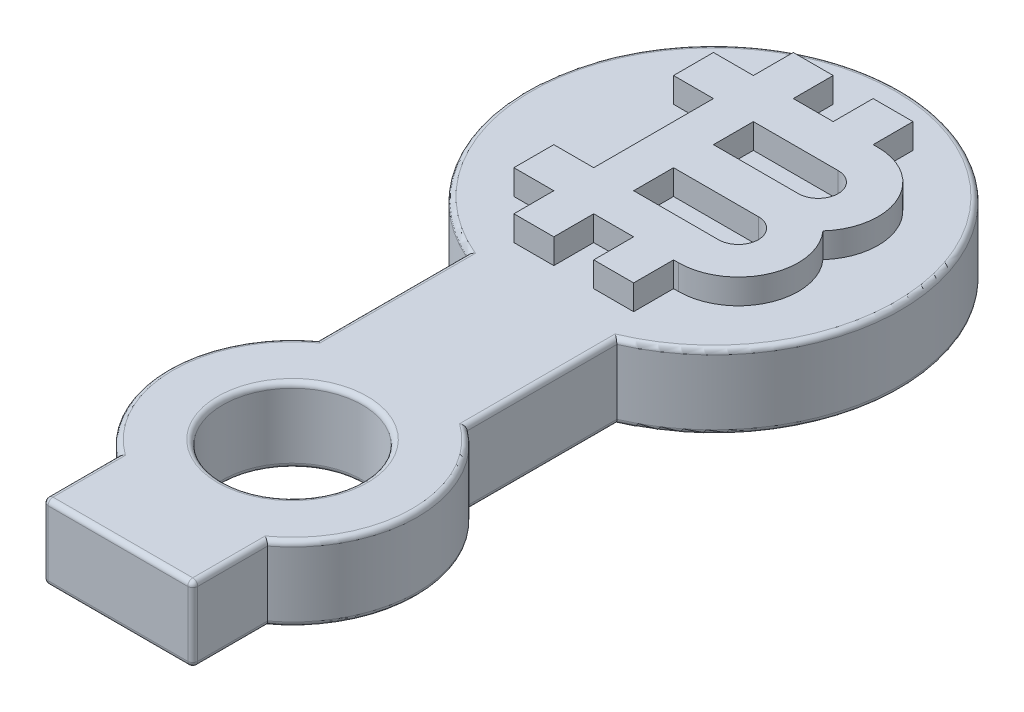
SolidWorks part; units mm, degrees
ref_plane "前视基准面" through (0, 0, 0) normal (0, 0, 1) x (1, 0, 0)
ref_plane "上视基准面" through (0, 0, 0) normal (0, 1, 0) x (1, 0, 0)
ref_plane "右视基准面" through (0, 0, 0) normal (1, 0, 0) x (0, 0, -1)
other "Configuration Table"
sketch "草图4" plane through (0, 0, 0) normal (0, 1, 0) x (1, 0, 0)
  line L0 (-3, 4) -> (-3, 10)
  line L2 (3, 10) -> (3, 4)
  line L3 (-3, -4) -> (-3, -7)
  line L4 (-3, -7) -> (3, -7)
  line L5 (3, -7) -> (3, -4)
  line L6 (0, 0) -> (0, 16.8739) construction
  circle A0 centre (0, 0) radius 2.8
  circle A1 centre (0, 0) radius 5
  circle A2 centre (0, 16.8739) radius 7.5
  dimension "D1" = 5.6
  dimension "D2" = 10
  dimension "D3" = 15
  dimension "D4" = 6
  dimension "D5" = 3
  dimension "D6" = 6
extrude "凸台-拉伸2" add sketch "草图4" along normal blind 3 contours A2 | A1 L6 A2 L0 | L6 A1 L2 A2 | A0 A1 | A1 L3 L4 L5 region at (-1.5364, 0, -4.6093) region at (-1.5815, 0, -7.1249) region at (-3.9917, 0, -22.9713) region at (0, 0, 5.8221) region at (1.5815, 0, -7.1249)
fillet "圆角1" radius 0.2 20 edges at (0, 0, 2.8) (-5, 0, 0) (-3, 0, 5.5) (0, 0, 7) (3, 0, 5.5) (5, 0, 0) (3, 0, -7) (0, 0, -24.3739) (-3, 0, -7) (0, 3, -24.3739) (3, 3, -7) (5, 3, 0) (3, 3, 5.5) (0, 3, 7) (-3, 3, 5.5) (-5, 3, 0) (-3, 3, -7) (0, 3, 2.8) (3, 1.5, 7) (-3, 1.5, 7)
sketch "草图1" plane through (0, 3, 0) normal (0, 1, 0) x (1, 0, 0)
  line L1 (-15.5883, 16.8739) -> (31.6232, 16.8739) construction
  line L2 (-0.8, 17.6739) -> (2.6, 17.6739)
  line L3 (-0.8, 17.6739) -> (-0.8, 19.2739)
  line L4 (-0.8, 19.2739) -> (2.6, 19.2739)
  line L5 (2.6, 16.0739) -> (-0.8, 16.0739)
  line L6 (-0.8, 16.0739) -> (-0.8, 14.4739)
  line L7 (-0.8, 14.4739) -> (2.6, 14.4739)
  line L9 (-0.8, 22.4739) -> (-2.4, 22.4739)
  line L10 (-2.4, 22.4739) -> (-2.4, 20.8739)
  line L11 (-2.4, 20.8739) -> (-4, 20.8739)
  line L12 (-4, 20.8739) -> (-4, 19.2739)
  line L13 (-4, 19.2739) -> (-2.4, 19.2739)
  line L14 (-2.4, 19.2739) -> (-2.4, 14.4739)
  line L15 (-4, 14.4739) -> (-4, 12.8739)
  line L16 (-4, 12.8739) -> (-2.4, 12.8739)
  line L17 (-2.4, 14.4739) -> (-4, 14.4739)
  line L18 (2.4, 20.8739) -> (2.6, 20.8739)
  line L19 (-2.4, 12.8739) -> (-2.4, 11.2739)
  line L20 (-2.4, 11.2739) -> (-0.8, 11.2739)
  line L22 (2.4, 12.8739) -> (2.6, 12.8739)
  line L23 (-0.8, 22.4739) -> (-0.8, 20.8739)
  line L24 (-0.8, 20.8739) -> (0.8, 20.8739)
  line L25 (0.8, 20.8739) -> (0.8, 22.4739)
  line L26 (0.8, 22.4739) -> (2.4, 22.4739)
  line L28 (2.4, 12.8739) -> (2.4, 11.2739)
  line L29 (2.4, 11.2739) -> (0.8, 11.2739)
  line L30 (0.8, 11.2739) -> (0.8, 12.8739)
  line L31 (0.8, 12.8739) -> (-0.8, 12.8739)
  line L32 (-0.8, 12.8739) -> (-0.8, 11.2739)
  line L33 (2.4, 20.8739) -> (2.4, 22.4739)
  arc A0 (2.6, 19.2739) -> (2.6, 17.6739) centre (2.6, 18.4739) cw
  arc A1 (2.6, 16.0739) -> (2.6, 14.4739) centre (2.6, 15.2739) cw
  arc A2 (2.6, 20.8739) -> (4.3889, 16.8739) centre (2.6, 18.4739) cw
  arc A3 (2.6, 12.8739) -> (4.3889, 16.8739) centre (2.6, 15.2739) ccw
  arc A4 (-3, 10) -> (3, 23.7477) centre (0, 16.8739) ccw construction
  arc A5 (-3, 10) -> (3, 23.7477) centre (0, 16.8739) ccw construction
  point P69 (0, 20.8739)
  dimension "D1" = 1.6
  dimension "D2" = 1.6
  dimension "D3" = 1.6
  dimension "D4" = 1.6
  dimension "D5" = 1.6
  dimension "D6" = 1.6
  dimension "D7" = 1.6
  dimension "D8" = 1.6
  dimension "D9" = 1.6
  dimension "D10" = 1.6
  dimension "D11" = 1.6
  dimension "D13" = 0.2
extrude "凸台-拉伸3" add sketch "草图1" along normal blind 1
equation "\"btc_min_width\"= 1.6mm"
equation "\"D1@草图1\"=\"btc_min_width\""
equation "\"D8@草图1\"=\"btc_min_width\""
equation "\"D11@草图1\"=\"btc_min_width\""
equation "\"D9@草图1\"=\"btc_min_width\""
equation "\"D2@草图1\"=\"btc_min_width\""
equation "\"D6@草图1\"=\"btc_min_width\""
equation "\"D4@草图1\"=\"btc_min_width\""
equation "\"D3@草图1\"=\"btc_min_width\""
equation "\"D5@草图1\"=\"btc_min_width\""
equation "\"D7@草图1\"=\"btc_min_width\""
equation "\"D10@草图1\"=\"btc_min_width\""
